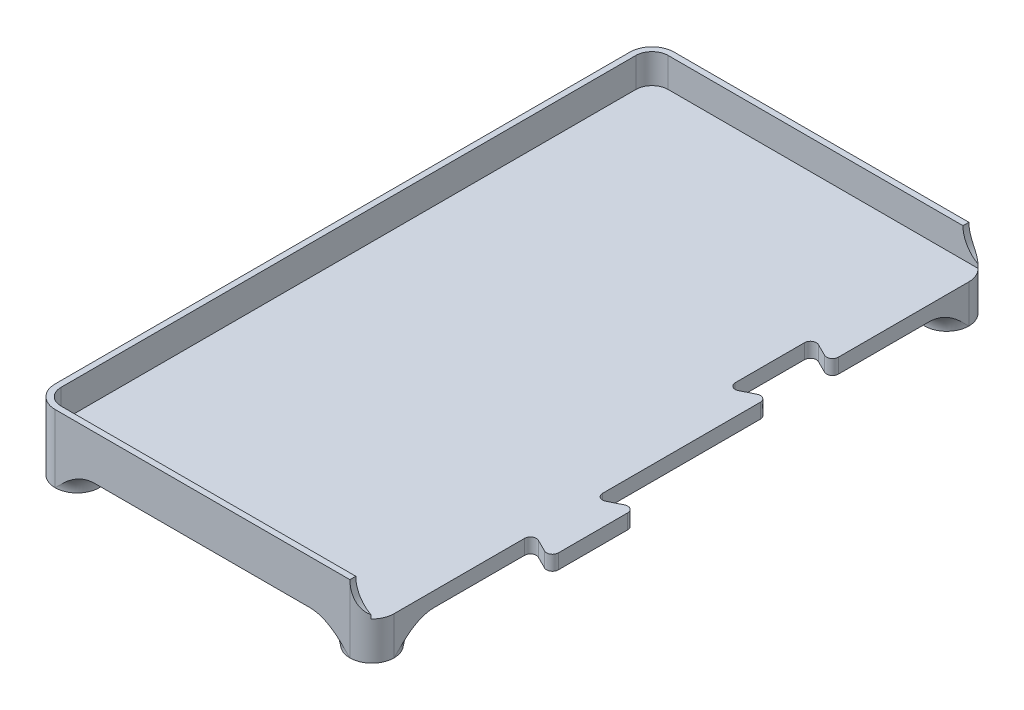
SolidWorks part; units mm, degrees
ref_plane "Спереди" through (0, 0, 0) normal (0, 0, 1) x (1, 0, 0)
ref_plane "Сверху" through (0, 0, 0) normal (0, 1, 0) x (1, 0, 0)
ref_plane "Справа" through (0, 0, 0) normal (1, 0, 0) x (0, 0, -1)
other "Configuration Table"
sketch "Эскиз1" plane through (0, 0, 0) normal (0, 1, 0) x (1, 0, 0)
  line L0 (0, 105) -> (0, -110.1763) construction
  line L1 (-50, -105) -> (50, -105)
  line L2 (-57.5, -97.5) -> (-57.5, 97.5)
  line L3 (-50, 105) -> (50, 105)
  line L4 (57.5, -97.5) -> (57.5, 97.5)
  line L5 (47.5, 55) -> (57.5, 50)
  line L7 (-57.5, 0) -> (57.5, 0) construction
  line L10 (47.5, 55) -> (47.5, 25)
  line L14 (67.5, -25) -> (67.5, -55)
  line L15 (47.5, 25) -> (57.5, 30)
  line L16 (67.5, -25) -> (57.5, -30)
  line L17 (67.5, -55) -> (57.5, -50)
  circle A0 centre (-50, -97.5) radius 7.5
  circle A1 centre (50, -97.5) radius 7.5
  circle A2 centre (50, 97.5) radius 7.5
  circle A3 centre (-50, 97.5) radius 7.5
  circle A4 centre (-50, -97.5) radius 5
  circle A5 centre (50, -97.5) radius 5
  circle A6 centre (50, 97.5) radius 5
  circle A7 centre (-50, 97.5) radius 5
  point P0 (0, 0)
  dimension "D3" = 15
  dimension "D4" = 10
  dimension "D1" = 210
  dimension "D2" = 115
  dimension "D5" = 50
  dimension "D6" = 20
  dimension "D7" = 5
  dimension "D8" = 5
  dimension "D9" = 10
  dimension "D10" = 50
  dimension "D11" = 5
  dimension "D12" = 20
  dimension "D13" = 5
  dimension "D14" = 10
extrude "Бобышка-Вытянуть1" add sketch "Эскиз1" along normal blind 5 contours A7 | A3 A7 | A6 | A2 A6 | A5 | A1 A5 | L3 A3 L2 A0 L1 A1 L4 A2 | A0 A4 | A4 region at (-0.5635, 0, 0.4321) region at (-55.1533, 0, 102.6533) region at (44.8467, 0, 92.3467) region at (-55.1533, 0, -102.6533) region at (55.1533, 0, -102.6533) region at (-50, 0, 97.5) region at (50, 0, 97.5) region at (50, 0, -97.5) region at (-50, 0, -97.5)
extrude "Бобышка-Вытянуть3" add sketch "Эскиз1<4>" against normal blind 8 contours A0 A4 region at (-55.1533, 0, 102.6533)
sketch "Эскиз1<4>" plane through (0, 0, 0) normal (0, 1, 0) x (1, 0, 0) same geometry as "Эскиз1"
fillet "Скругление1" radius 8 1 edges at (-44.6967, 0, 92.1967)
mirror "Зеркальное отражение4" about plane through (0, 0, 0) normal (1, 0, 0) of "Бобышка-Вытянуть3"
mirror "Зеркальное отражение5" about plane through (0, 0, 0) normal (0, 0, 1) of "Зеркальное отражение4"
fillet "Скругление2" radius 8 1 edges at (44.6967, 0, 92.1967)
fillet "Скругление3" radius 8 1 edges at (44.6967, 0, -92.1967)
fillet "Скругление4" radius 8 1 edges at (-44.6967, 0, -92.1967)
extrude "Бобышка-Вытянуть4" add sketch "Эскиз1<5>" along normal blind 5 contours L17 L14 L16 L4 region at (62.8333, 0, 40)
sketch "Эскиз1<5>" plane through (0, 0, 0) normal (0, 1, 0) x (1, 0, 0) same geometry as "Эскиз1"
fillet "Скругление5" radius 2 8 edges at (57.5, 2.5, 30) (47.5, 2.5, -25) (57.5, 2.5, 50) (67.5, 2.5, 55) (67.5, 2.5, 25) (57.5, 2.5, -30) (47.5, 2.5, -55) (57.5, 2.5, -50)
sketch "Эскиз2" plane through (0, 5, 0) normal (0, 1, 0) x (1, 0, 0)
  line L11 (50, -103) -> (-50, -103)
  line L12 (-55.5, -97.5) -> (-55.5, 97.5)
  line L13 (50, 103) -> (-50, 103)
  line L15 (50, 105) -> (50, 103)
  line L16 (50, -103) -> (50, -105)
  line L17 (-50, -105) -> (-50, -97.5) construction
  line L18 (-57.5, -97.5) -> (-50, -97.5) construction
  line L20 (-50, 105) -> (-50, 97.5) construction
  line L21 (-57.5, 97.5) -> (-50, 97.5) construction
  line L25 (50, -105) -> (-50, -105)
  line L27 (50, 105) -> (-50, 105)
  line L28 (-57.5, -97.5) -> (-57.5, 97.5)
  arc A0 (-50, -105) -> (-57.5, -97.5) centre (-50, -97.5) cw
  arc A1 (-50, 105) -> (-57.5, 97.5) centre (-50, 97.5) ccw
  arc A2 (-50, -103) -> (-55.5, -97.5) centre (-50, -97.5) cw
  arc A3 (-50, 103) -> (-55.5, 97.5) centre (-50, 97.5) ccw
  point P4 (-50, -97.6037)
  point P9 (-50.0793, 97.5)
  point P10 (0, 0)
  point P12 (0, 0)
  point P13 (-50, -97.5)
  point P21 (-50, 97.4123)
  point P22 (-50, 97.5)
  point P23 (-50.1119, -97.5)
  line M33 (50, 105) -> (-50, 105)
  arc M34 (-50, 105) -> (-57.5, 97.5) centre (-50, 97.5) ccw
  line M35 (-57.5, 97.5) -> (-57.5, -97.5)
  arc M36 (-57.5, -97.5) -> (-50, -105) centre (-50, -97.5) ccw
  line M37 (-50, -105) -> (50, -105)
  dimension "D1" = 2
  dimension "D2" = 57.5
extrude "Бобышка-Вытянуть5" add sketch "Эскиз2" along normal blind 10 contours A3 L13 L15 L16 L11 A2 L12 M33 M34 M35 M36 M37 region at (47.6408, 5, 104)
fillet "Скругление6" radius 10 2 edges at (50, 5, 104) (50, 5, -104)
